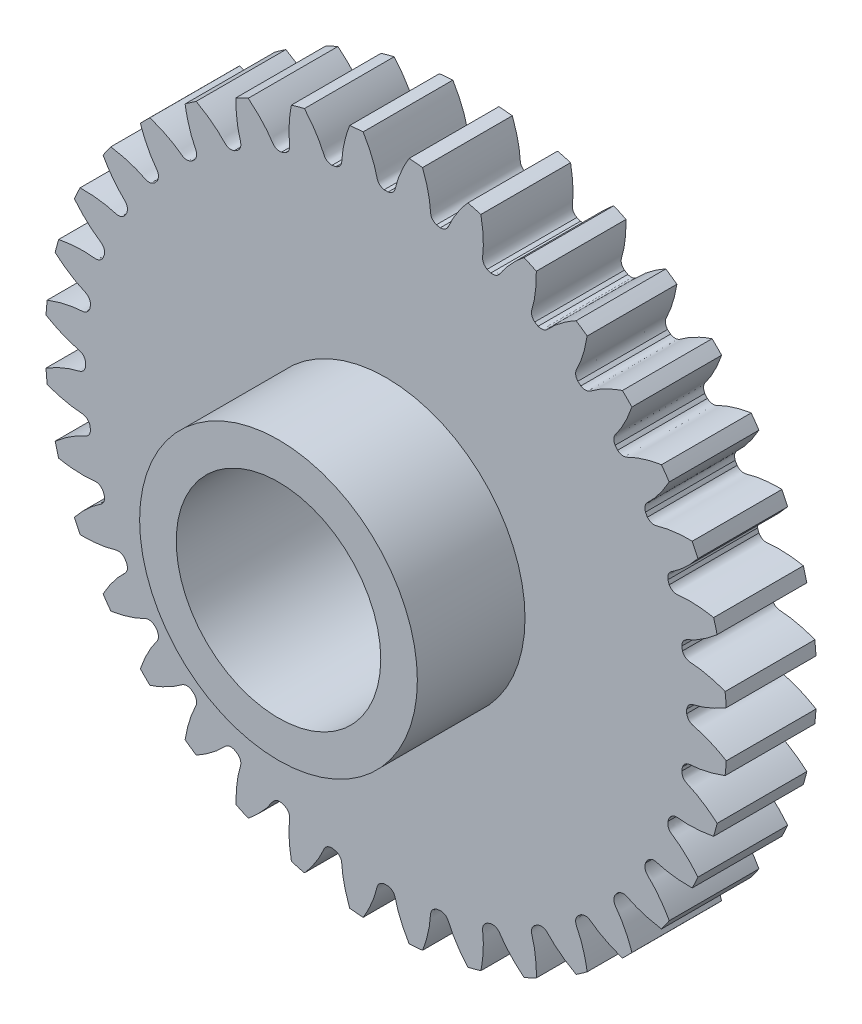
SolidWorks part; units mm, degrees
ref_plane "前视基准面" through (0, 0, 0) normal (0, 0, 1) x (1, 0, 0)
ref_plane "上视基准面" through (0, 0, 0) normal (0, 1, 0) x (1, 0, 0)
ref_plane "右视基准面" through (0, 0, 0) normal (1, 0, 0) x (0, 0, -1)
other "Configuration Table"
sketch "草图1" plane through (0, 0, 0) normal (0, 0, 1) x (1, 0, 0)
  circle A0 centre (0, 0) radius 9.5
extrude "凸台-拉伸1" add sketch "草图1" along normal blind 2.5
ref_axis "基准轴1" through (0, 0, 2.5) along (0, 0, -1)
sketch "草图2" plane through (0, 0, 0) normal (0, 0, 1) x (1, 0, 0)
  line L0 (0, 0) -> (0, 9.5) construction
  circle A0 centre (0, 0) radius 9.5 construction
  arc A1 (0.0549, 8.3748) -> (-0.0549, 8.3748) centre (0, 0) ccw
  arc A2 (1.757, 10.7884) -> (-1.757, 10.7884) centre (0, 0) ccw
  spline S0 degree 3 poles (0.0549, 8.3748) (0.235, 8.4152) (0.2505, 8.5493) (0.2882, 8.6914) (0.2997, 8.7319) (0.3131, 8.7753) (0.3284, 8.8217) (0.3457, 8.871) (0.3652, 8.9231) (0.3869, 8.9779) (0.4111, 9.0354) (0.4378, 9.0956) (0.4671, 9.1582) (0.4992, 9.2232) (0.5341, 9.2907) (0.5719, 9.3603) (0.6128, 9.4322) (0.6569, 9.5061) (0.7043, 9.582) (0.755, 9.6598) (0.8091, 9.7393) (0.8668, 9.8205) (0.9281, 9.9032) (0.9931, 9.9874) (1.0619, 10.0729) (1.1346, 10.1596) (1.2112, 10.2474) (1.2919, 10.3361) (1.3766, 10.4256) (1.4655, 10.5159) (1.5912, 10.6386) (1.6895, 10.7288) (1.757, 10.7884) knots 0 0 0 0 0.120371 0.133303 0.147364 0.162556 0.178878 0.19633 0.214913 0.234626 0.255469 0.277443 0.300547 0.324782 0.350146 0.376641 0.404267 0.433023 0.462909 0.493925 0.526072 0.559349 0.593757 0.629294 0.665963 0.703761 0.74269 0.782749 0.823939 0.866258 0.909709 1 1 1 1
  spline S1 degree 3 poles (-0.0549, 8.3748) (-0.235, 8.4152) (-0.2505, 8.5493) (-0.2882, 8.6914) (-0.2997, 8.7319) (-0.3131, 8.7753) (-0.3284, 8.8217) (-0.3457, 8.871) (-0.3652, 8.9231) (-0.3869, 8.9779) (-0.4111, 9.0354) (-0.4378, 9.0956) (-0.4671, 9.1582) (-0.4992, 9.2232) (-0.5341, 9.2907) (-0.5719, 9.3603) (-0.6128, 9.4322) (-0.6569, 9.5061) (-0.7043, 9.582) (-0.755, 9.6598) (-0.8091, 9.7393) (-0.8668, 9.8205) (-0.9281, 9.9032) (-0.9931, 9.9874) (-1.0619, 10.0729) (-1.1346, 10.1596) (-1.2112, 10.2474) (-1.2919, 10.3361) (-1.3766, 10.4256) (-1.4655, 10.5159) (-1.5912, 10.6386) (-1.6895, 10.7288) (-1.757, 10.7884) knots 0 0 0 0 0.120371 0.133303 0.147364 0.162556 0.178878 0.19633 0.214913 0.234626 0.255469 0.277443 0.300547 0.324782 0.350146 0.376641 0.404267 0.433023 0.462909 0.493925 0.526072 0.559349 0.593757 0.629294 0.665963 0.703761 0.74269 0.782749 0.823939 0.866258 0.909709 1 1 1 1
extrude "切除-拉伸1" cut sketch "草图2" along normal through all
pattern_circular "阵列(圆周)1" count 36 every 10 about axis through (0, 0, 2.5) along (0, 0, -1) of "切除-拉伸1"
sketch "草图3" plane through (0, 0, 0) normal (0, 0, 1) x (1, 0, 0)
  circle A0 centre (0, 0) radius 9 construction
  dimension "Dn" = 18
sketch "草图4" plane through (0, 0, 0) normal (0, 0, -1) x (-1, 0, 0)
  circle A0 centre (0, 0) radius 3.87
  dimension "D1" = 7.74
extrude "凸台-拉伸2" add sketch "草图4" against normal offset from surface (5.5 mm away) 3 up to face at (0, 0, 2.5) offset beyond the face yes
sketch "草图5" plane through (0, 0, 5.5) normal (0, 0, 1) x (1, 0, 0)
  circle A0 centre (0, 0) radius 2.85
  dimension "D1" = 5.7
extrude "切除-拉伸2" cut sketch "草图5" against normal up to next
